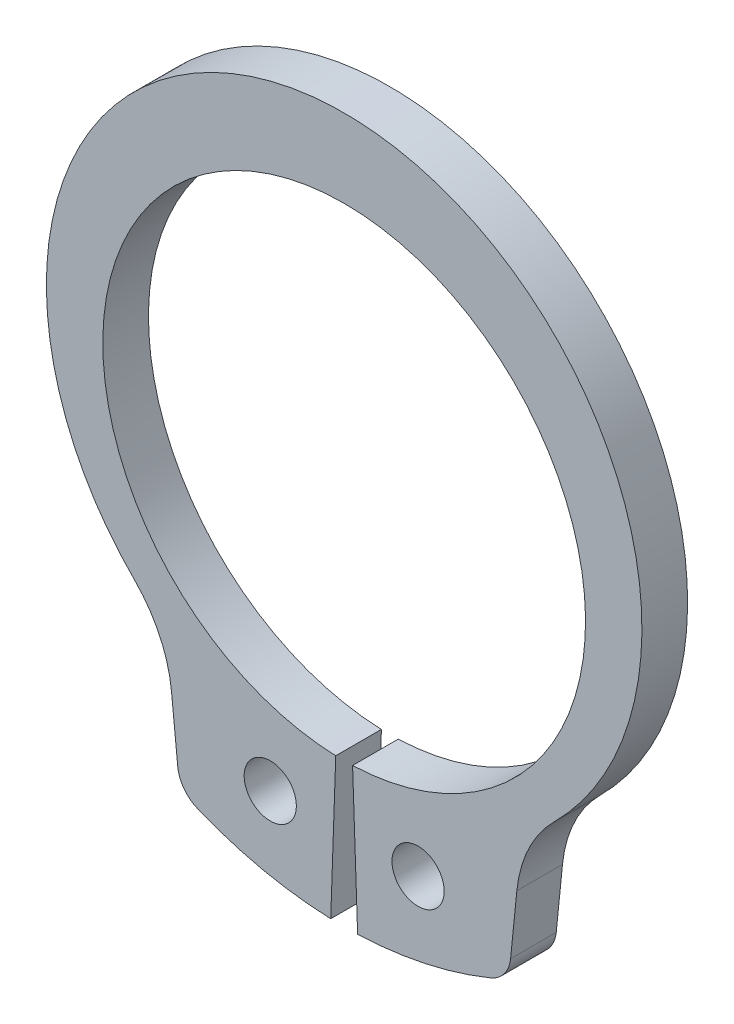
SolidWorks part; units mm, degrees
ref_plane "Front" through (0, 0, 0) normal (0, 0, 1) x (1, 0, 0)
ref_plane "Top" through (0, 0, 0) normal (0, 1, 0) x (1, 0, 0)
ref_plane "Right" through (0, 0, 0) normal (1, 0, 0) x (0, 0, -1)
sketch "Sketch1" plane through (0, 0, 0) normal (0, 0, 1) x (1, 0, 0)
  line L0 (0, 0) -> (-8.0107, -4.625) construction
  line L1 (0, 14.75) -> (0, -14.75) construction
  line L2 (-6.3056, -13.3442) -> (-6.8124, -8.3159) construction
  line L4 (-6.8124, -8.3159) -> (-7.7629, -9.4763) construction
  line L5 (-6.8124, -8.3159) -> (0, 0) construction
  line L6 (0, 9.25) -> (0, 12.25) construction
  line L7 (0, 12.25) -> (0, 10.75) construction
  line L8 (0, -9.25) -> (0, -14.75) construction
  line L9 (-3.482, -14.3424) -> (0, 0) construction
  line L10 (0, 0) -> (-0.5151, -14.75) construction
  line L11 (-6.3056, -13.3442) -> (0, 0) construction
  line L12 (-6.6504, -9.9229) -> (-8.0366, -7.2624) construction
  line L13 (-7.3435, -8.5927) -> (-6.8124, -8.3159) construction
  line L14 (-2.1823, -8.9889) -> (-3.482, -14.3424) construction
  line L15 (-2.8322, -11.6656) -> (-1.8604, -11.9015) construction
  arc A0 (0, 12.25) -> (-6.8124, -8.3159) centre (0, 0.8388) ccw construction
  circle A2 centre (0, 0) radius 12.25 construction
  arc A3 (-6.3056, -13.3442) -> (-0.5151, -14.75) centre (0, 0) ccw construction
  circle A4 centre (0, 0) radius 9.25 construction
  circle A6 centre (-2.8322, -11.6656) radius 1 construction
  arc A7 (-8.0366, -7.2624) -> (-6.6504, -9.9229) centre (-11.5097, -10.7634) cw construction
  point P5 (-8.0107, -4.625)
  point P24 (-5.2337, -11.0757)
  point P35 (0, 12.25)
  point P36 (0, 9.25)
  point P37 (0, -9.25)
  point P38 (0, -14.75)
  dimension "Ring ID" = 18.5
  dimension "Hole Diameter" = 2
  dimension "D10" = 4.9315
  dimension "Max Sec." = 3
  dimension "Lug Height" = 5.5
  dimension "D6" = 2
  dimension "D5" = 5.0537
  dimension "D8" = 3
  dimension "D3" = 120
  dimension "D2" = 6
  dimension "D4" = 3
sketch "Sketch5" plane through (0, 0, 0) normal (0, 1, 0) x (1, 0, 0)
  line L0 (-12.25, 0.875) -> (-12.25, -0.875) construction
  line L2 (0, 0.875) -> (0, -0.875) construction
  line L4 (-12.25, 0) -> (12.25, 0) construction
  point P3 (-12.25, 0)
  point P6 (0, 0)
  dimension "Ring Thickness" = 1.75
sketch "Sketch2" plane through (0, 0, 0) normal (0, 0, 1) x (1, 0, 0)
  line L0 (-6.3056, -13.3442) -> (-6.8124, -8.3159) construction
  line L1 (-6.3056, -13.3442) -> (-6.8124, -8.3159)
  line L2 (0, 12.25) -> (0, 9.25)
  line L3 (-0.5151, -14.75) -> (-0.3228, -9.2444)
  line L4 (0, 0) -> (-0.5151, -14.75) construction
  arc A0 (0, 12.25) -> (-6.8124, -8.3159) centre (0, 0.8388) ccw construction
  arc A1 (-6.3056, -13.3442) -> (-0.5151, -14.75) centre (0, 0) ccw construction
  circle A2 centre (-2.8322, -11.6656) radius 1 construction
  arc A4 (0, 12.25) -> (-6.8124, -8.3159) centre (0, 0.8388) ccw
  arc A5 (-6.3056, -13.3442) -> (-0.5151, -14.75) centre (0, 0) ccw
  circle A6 centre (-2.8322, -11.6656) radius 1
  circle A7 centre (0, 0) radius 9.25 construction
  arc A8 (0, 9.25) -> (-0.3228, -9.2444) centre (0, 0) ccw
extrude "Boss-Extrude1" add sketch "Sketch2" along normal mid plane 1.75
fillet "Fillet1" radius 4.9315 1 edges at (-6.8124, -8.3159, 0)
fillet "Fillet2" radius 1.2329 1 edges at (-6.3056, -13.3442, 0)
mirror "Mirror1" about plane through (0, 12.25, 0.875) normal (-1, 0, 0) of bodies 109
sketch "Sketch3" plane through (0, 0, 0.875) normal (0, 0, 1) x (1, 0, 0)
  line L0 (6.9284, -6.1286) -> (8.0463, -7.2528) construction
  line L1 (8.0463, -7.2528) -> (9.1705, -6.1349) construction
  line L2 (0, 12.25) -> (0, 9.25) construction
  circle A0 centre (0, 0) radius 9.25 construction
  arc A1 (8.0463, -7.2528) -> (-8.0463, -7.2528) centre (0, 0.8388) ccw construction
equation "\"D1@Fillet1\" = \"D10@Sketch1\""
equation "\"D1@Fillet2\" = \"D10@Sketch1\" / 4"
equation "\"Thickness@Boss-Extrude1\"=\"Ring Thickness@Sketch5\""
equation "\"D2@Sketch1\"=\"Hole Diameter@Sketch1\"*3"
equation "\"D4@Sketch1\"=\"D2@Sketch1\"/2"
equation "\"D8@Sketch1\"=\"D4@Sketch1\""
